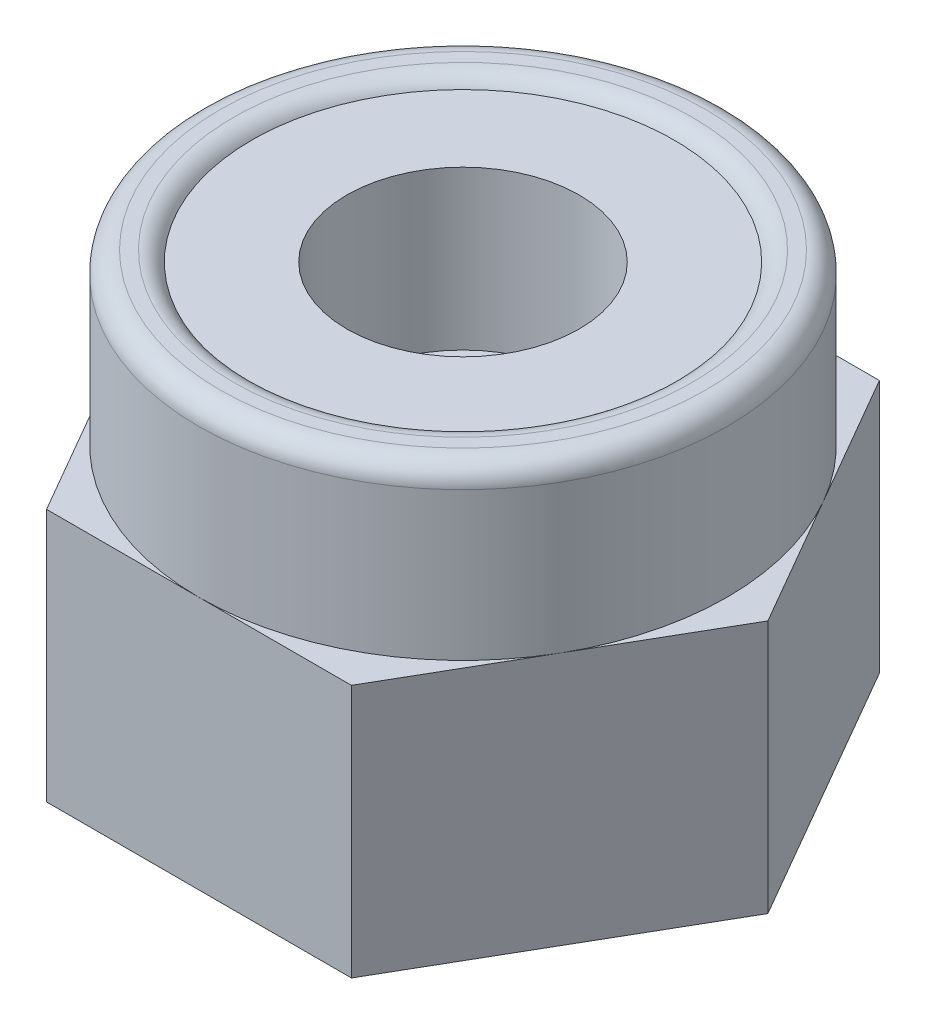
SolidWorks part; units mm, degrees
material "acero"
ref_plane "Alzado" through (0, 0, 0) normal (0, 0, 1) x (1, 0, 0)
ref_plane "Planta" through (0, 0, 0) normal (0, 1, 0) x (1, 0, 0)
ref_plane "Vista lateral" through (0, 0, 0) normal (1, 0, 0) x (0, 0, -1)
sketch "Croquis1" plane through (0, 0, 0) normal (0, 1, 0) x (1, 0, 0)
  line L1 (-1.4434, 2.5) -> (-2.8868, 0)
  line L2 (-2.8868, 0) -> (-1.4434, -2.5)
  line L3 (-1.4434, -2.5) -> (1.4434, -2.5)
  line L4 (1.4434, -2.5) -> (2.8868, 0)
  line L5 (2.8868, 0) -> (1.4434, 2.5)
  line L6 (1.4434, 2.5) -> (-1.4434, 2.5)
  circle A0 centre (0, 0) radius 2.5 construction
  circle A1 centre (0, 0) radius 1
  dimension "D1" = 2
  dimension "D2" = 5
extrude "Saliente-Extruir1" add sketch "Croquis1" along normal blind 2.4
sketch "Croquis2" plane through (0, 2.4, 0) normal (0, 1, 0) x (1, 0, 0)
  line L0 (2.8868, 0) -> (1.4434, 2.5) construction
  circle A0 centre (0, 0) radius 2.5
  circle A1 centre (0, 0) radius 1.1
  dimension "D1" = 2.2
extrude "Saliente-Extruir2" add sketch "Croquis2" along normal blind 1.6
sketch "Croquis4" plane through (0, 4, 0) normal (0, 1, 0) x (1, 0, 0)
  circle A0 centre (0, 0) radius 1.1 construction
  circle A1 centre (0, 0) radius 1.1
  circle A2 centre (0, 0) radius 2
  dimension "D1" = 4
extrude "Cortar-Extruir1" cut sketch "Croquis4" against normal blind 0.1
fillet "Redondeo1" radius 0.2 2 edges at (0, 4, 2.5) (0, 4, 2)
